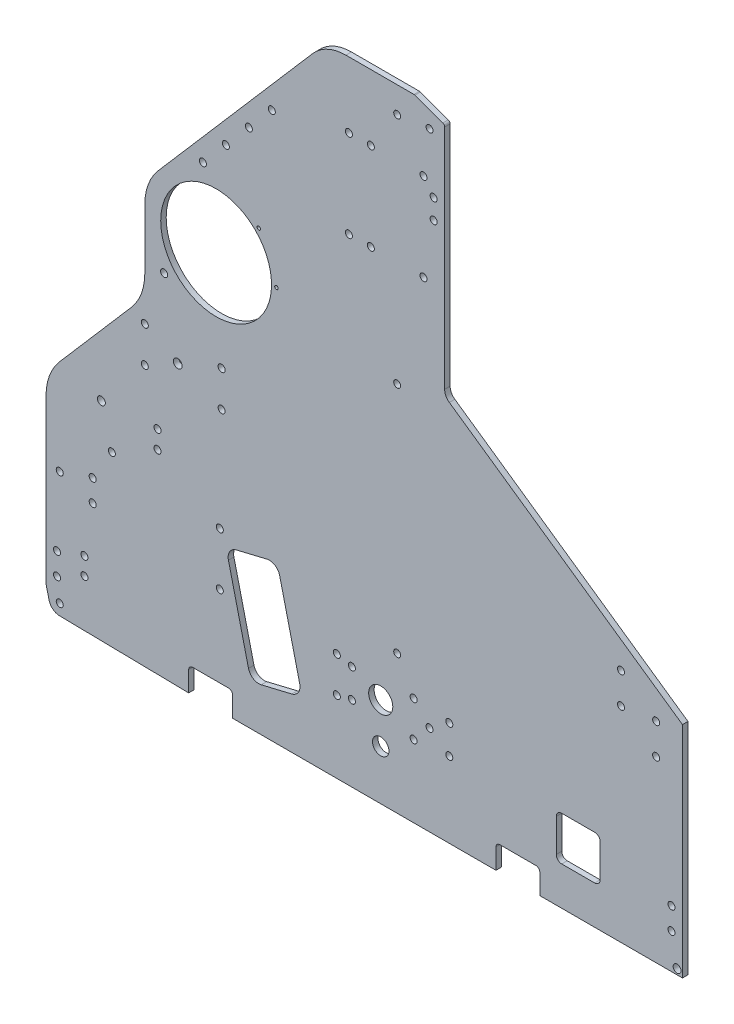
SolidWorks part; units mm, degrees
ref_plane "Front Plane" through (0, 0, 0) normal (0, 0, 1) x (1, 0, 0)
ref_plane "Top Plane" through (0, 0, 0) normal (0, 1, 0) x (1, 0, 0)
ref_plane "Right Plane" through (0, 0, 0) normal (1, 0, 0) x (0, 0, -1)
sketch "Sketch1" plane through (0, 0, 0) normal (0, 0, 1) x (1, 0, 0)
  line L0 (82.55, -20.32) -> (82.55, -6.35)
  line L2 (0, 0) -> (0, 157.48)
  line L4 (368.3, -20.32) -> (368.3, 106.68)
  line L5 (82.55, -6.35) -> (107.95, -6.35)
  line L6 (107.95, -6.35) -> (107.95, -20.32)
  line L7 (107.95, -20.32) -> (260.35, -20.32)
  line L8 (260.35, -20.32) -> (260.35, -6.35)
  line L9 (260.35, -6.35) -> (285.75, -6.35)
  line L10 (285.75, -6.35) -> (285.75, -20.32)
  line L11 (285.75, -20.32) -> (368.3, -20.32)
  line L12 (361.95, 12.7) -> (368.3, 12.7) construction
  line L13 (0, 0) -> (6.35, 0) construction
  line L14 (0.1896, -7.8901) -> (1.7771, -14.2401)
  line L15 (7.8295, -19.0491) -> (82.55, -20.32)
  line L16 (0, 0) -> (0, -6.35)
  line L17 (76.2, 141.605) -> (79.375, 141.605) construction
  line L18 (57.15, 131.2863) -> (101.6, 131.2862) construction
  line L19 (57.15, 131.2863) -> (57.15, 151.9238) construction
  line L20 (101.6, 131.2862) -> (101.6, 151.9237) construction
  line L21 (57.15, 151.9238) -> (101.6, 151.9237) construction
  line L22 (57.15, 131.2863) -> (101.6, 151.9237) construction
  line L23 (101.6, 131.2862) -> (57.15, 151.9238) construction
  line L25 (203.2, 59.805) -> (203.2, 194.805) construction
  line L26 (203.2, 194.805) -> (203.2, 329.805) construction
  line L27 (355.6, 332.105) -> (330.2, 332.105) construction
  line L28 (330.2, 332.105) -> (330.2, 217.805) construction
  line L29 (330.2, 217.805) -> (355.6, 217.805) construction
  line L30 (355.6, 217.805) -> (355.6, 332.105) construction
  line L31 (203.2, 344.805) -> (203.2, 194.805) construction
  line L32 (50.8, 332.105) -> (76.2, 332.105) construction
  line L33 (76.2, 332.105) -> (76.2, 217.805) construction
  line L34 (50.8, 217.805) -> (50.8, 332.105) construction
  line L35 (76.2, 217.805) -> (50.8, 217.805) construction
  line L36 (213.2, 344.805) -> (230.6638, 338.455)
  line L37 (203.2, 344.805) -> (161.925, 344.805)
  line L38 (203.2, 344.805) -> (213.2, 344.805)
  line L39 (348.5362, 344.805) -> (413.4623, 344.805)
  line L40 (348.5362, 344.805) -> (230.6638, 344.805) construction
  line L42 (161.925, 344.805) -> (0, 157.48)
  line L44 (230.6638, 338.455) -> (230.6638, 202.565)
  line L45 (230.6638, 202.565) -> (368.3, 106.68)
  line L46 (213.2, 344.805) -> (-141.0713, 344.805) construction
  circle A0 centre (6.35, 0) radius 2.032
  circle A1 centre (6.35, 12.7) radius 2.032
  circle A2 centre (361.95, 0) radius 2.032
  circle A3 centre (361.95, 12.7) radius 2.032
  arc A5 (1.7771, -14.2401) -> (7.8295, -19.0491) centre (7.9375, -12.7) ccw
  circle A6 centre (7.9375, -12.7) radius 2.032
  arc A7 (0, -6.35) -> (0.1896, -7.8901) centre (6.35, -6.35) ccw
  circle A8 centre (38.1, 78.105) radius 2.032
  circle A9 centre (76.2, 141.605) radius 2.54
  circle A10 centre (101.6, 131.2862) radius 2.032
  circle A11 centre (101.6, 151.9237) radius 2.032
  circle A12 centre (57.15, 151.9238) radius 2.032
  circle A13 centre (57.15, 131.2863) radius 2.032
  circle A15 centre (203.2, 59.805) radius 2
  circle A16 centre (203.2, 194.805) radius 2
  circle A17 centre (203.2, 329.805) radius 2
  circle A18 centre (63.5, 313.055) radius 2.032
  circle A20 centre (355.6, 332.105) radius 2.032
  circle A21 centre (330.2, 332.105) radius 2.032
  circle A22 centre (355.6, 217.805) radius 2.032
  circle A23 centre (330.2, 217.805) radius 2.032
  circle A24 centre (50.8, 332.105) radius 2.032
  circle A25 centre (76.2, 332.105) radius 2.032
  circle A26 centre (50.8, 217.805) radius 2.032
  circle A27 centre (76.2, 217.805) radius 2.032
  circle A28 centre (221.9319, 332.105) radius 2
  circle A29 centre (224.3138, 298.831) radius 2.032
  circle A30 centre (353.06, 100.7351) radius 2.032
  circle A31 centre (332.74, 115.9751) radius 2.032
  circle A32 centre (332.74, 98.1951) radius 2.032
  circle A33 centre (353.06, 82.9551) radius 2.032
  circle A34 centre (117.3562, 280.4276) radius 2.032
  circle A35 centre (104.0678, 265.0548) radius 2.032
  circle A36 centre (90.7795, 249.682) radius 2.032
  circle A38 centre (130.6445, 295.8004) radius 2.032
  circle A39 centre (68.326, 182.9237) radius 2.032
  circle A40 centre (224.3138, 287.401) radius 2.032
  point P82 (203.2, 344.805)
  point P83 (221.9319, 341.63)
  point P90 (368.3, 62.484)
  dimension "D6" = 4.064
  dimension "D10" = 6.35
  dimension "D11" = 4.064
  dimension "D17" = 38.1
  dimension "D27" = 4
  dimension "D31" = 4.064
  dimension "D32" = 41.275
  dimension "D36" = 4.064
  dimension "D47" = 39.624
  dimension "D48" = 4.064
  dimension "D25" = 5.08
  dimension "D26" = 4.064
  dimension "D52" = 4.064
  dimension "D65" = 4.064
  dimension "D2" = 127
  dimension "D3" = 13.97
  dimension "D4" = 25.4
  dimension "D5" = 152.4
  dimension "D7" = 12.7
  dimension "D8" = 6.35
  dimension "D9" = 20.32
  dimension "D12" = 12.7
  dimension "D13" = 1.5875
  dimension "D14" = 82.55
  dimension "D15" = 368.3
  dimension "D16" = 6.35
  dimension "D18" = 98.425
  dimension "D19" = 38.1
  dimension "D20" = 63.5
  dimension "D21" = 3.175
  dimension "D22" = 270
  dimension "D23" = 20.6375
  dimension "D24" = 44.45
  dimension "D28" = 135
  dimension "D29" = 12.7
  dimension "D30" = 15
  dimension "D33" = 63.5
  dimension "D34" = 27.4638
  dimension "D35" = 12.7
  dimension "D37" = 114.3
  dimension "D38" = 25.4
  dimension "D39" = 12.7
  dimension "D40" = 157.48
  dimension "D41" = 142.24
  dimension "D42" = 365.125
  dimension "D43" = 10
  dimension "D44" = 6.35
  dimension "D45" = 31.75
  dimension "D46" = 6.35
  dimension "D49" = 6.35
  dimension "D50" = 203.2
  dimension "D51" = 15.24
  dimension "D53" = 17.78
  dimension "D54" = 17.78
  dimension "D55" = 20.32
  dimension "D56" = 15.24
  dimension "D57" = 92.202
  dimension "D58" = 8.382
  dimension "D59" = 20.32
  dimension "D60" = 20.32
  dimension "D61" = 8.382
  dimension "D62" = 20.32
  dimension "D63" = 8.382
  dimension "D64" = 8.382
  dimension "D66" = 35.052
  dimension "D67" = 68.326
  dimension "D68" = 11.43
extrude "Boss-Extrude1" add sketch "Sketch1" along normal blind 3.175 contours L16 A7 L14 A5 L15 L2 A0 A1 A6 region at (171.3489, 119.5243, 0)
fillet "Fillet1" radius 2.286 4 edges at (285.75, -6.35, 1.5875) (107.95, -6.35, 1.5875) (260.35, -6.35, 1.5875) (82.55, -6.35, 1.5875)
fillet "Fillet2" radius 6.35 1 edges at (230.6638, 202.565, 1.5875)
sketch "Sketch2" plane through (0, 0, 0) normal (0, 0, -1) x (-1, 0, 0)
  circle A0 centre (-100.5528, 71.086) radius 2.032 construction
  circle A1 centre (-100.5528, 40.606) radius 2.032 construction
  circle A2 centre (-22.225, 18.2025) radius 2.032 construction
  circle A3 centre (-22.225, 8.0425) radius 2.032 construction
  circle A4 centre (-100.5528, 71.086) radius 2.032
  circle A5 centre (-100.5528, 40.606) radius 2.032
  circle A6 centre (-22.225, 18.2025) radius 2.032
  circle A7 centre (-22.225, 8.0425) radius 2.032
extrude "Cut-Extrude1" cut sketch "Sketch2" against normal through all
fillet "Fillet3" radius 1.5875 2 edges at (230.6638, 338.455, 1.5875) (213.2, 344.805, 1.5875)
sketch "Sketch3" plane through (0, 0, 3.175) normal (0, 0, 1) x (1, 0, 0)
  line L0 (132.9524, 63.2646) -> (132.7215, 64.2281) construction
  line L1 (128.3814, 66.8897) -> (110.6828, 62.6472) construction
  line L2 (114.5132, 58.4237) -> (126.8822, 61.3887) construction
  line L3 (108.0212, 58.3071) -> (108.2522, 57.3436) construction
  line L4 (131.2006, 57.703) -> (140.0164, 20.9265) construction
  line L5 (144.0993, 16.7636) -> (132.9524, 63.2646) construction
  line L6 (108.2522, 57.3436) -> (119.3991, 10.8426) construction
  line L7 (121.1509, 16.4042) -> (112.3351, 53.1807) construction
  line L8 (119.3991, 10.8426) -> (119.6301, 9.8791) construction
  line L9 (144.3303, 15.8001) -> (144.0993, 16.7636) construction
  line L10 (137.8383, 15.6835) -> (125.4694, 12.7185) construction
  line L11 (123.9701, 7.2175) -> (141.6687, 11.4601) construction
  line L12 (132.9524, 63.2646) -> (132.7215, 64.2281)
  line L13 (128.3814, 66.8897) -> (110.6828, 62.6472)
  line L14 (114.5132, 58.4237) -> (126.8822, 61.3887)
  line L15 (108.0212, 58.3071) -> (108.2522, 57.3436)
  line L16 (131.2006, 57.703) -> (140.0164, 20.9265)
  line L17 (144.0993, 16.7636) -> (132.9524, 63.2646)
  line L18 (108.2522, 57.3436) -> (119.3991, 10.8426)
  line L19 (121.1509, 16.4042) -> (112.3351, 53.1807)
  line L20 (119.3991, 10.8426) -> (119.6301, 9.8791)
  line L21 (144.3303, 15.8001) -> (144.0993, 16.7636)
  line L22 (137.8383, 15.6835) -> (125.4694, 12.7185)
  line L23 (123.9701, 7.2175) -> (141.6687, 11.4601)
  line L24 (127.7894, 69.3598) -> (110.0908, 65.1172)
  line L25 (105.5512, 57.715) -> (105.7822, 56.7515)
  line L26 (105.7822, 56.7515) -> (116.9291, 10.2505)
  line L27 (116.9291, 10.2505) -> (117.16, 9.287)
  line L28 (124.5622, 4.7475) -> (142.2608, 8.99)
  line L29 (146.8003, 16.3922) -> (146.5694, 17.3557)
  line L30 (146.5694, 17.3557) -> (135.4225, 63.8567)
  line L31 (135.4225, 63.8567) -> (135.1915, 64.8202)
  line L32 (14.605, -0.1369) -> (103.7278, 32.3011) construction
  line L33 (14.605, -0.1369) -> (103.7278, 32.3011)
  line L34 (0, -6.35) -> (0, 157.48) construction
  line L35 (-39.6666, 74.7152) -> (103.7278, 126.9065) construction
  line L36 (26.9875, 46.9531) -> (26.9875, 59.6531) construction
  line L37 (107.95, -20.32) -> (260.35, -20.32) construction
  line L38 (64.5259, 92.5258) -> (64.5259, 102.9405) construction
  arc A0 (132.7215, 64.2281) -> (128.6308, 66.9403) centre (129.2206, 63.3889) ccw construction
  arc A1 (110.6828, 62.6472) -> (110.4377, 62.5791) centre (111.522, 59.1463) ccw construction
  arc A2 (128.6308, 66.9403) -> (128.3814, 66.8897) centre (129.2206, 63.3889) ccw construction
  arc A3 (110.4377, 62.5791) -> (108.0212, 58.3071) centre (111.522, 59.1463) ccw construction
  arc A4 (119.6301, 9.8791) -> (123.7207, 7.1669) centre (123.1309, 10.7183) ccw construction
  arc A5 (141.9139, 11.5281) -> (144.3303, 15.8001) centre (140.8295, 14.9609) ccw construction
  arc A6 (141.6687, 11.4601) -> (141.9139, 11.5281) centre (140.8295, 14.9609) ccw construction
  arc A7 (123.7207, 7.1669) -> (123.9701, 7.2175) centre (123.1309, 10.7183) ccw construction
  arc A8 (132.7215, 64.2281) -> (128.6308, 66.9403) centre (129.2206, 63.3889) ccw
  arc A9 (110.6828, 62.6472) -> (110.4377, 62.5791) centre (111.522, 59.1463) ccw
  arc A10 (128.6308, 66.9403) -> (128.3814, 66.8897) centre (129.2206, 63.3889) ccw
  arc A11 (110.4377, 62.5791) -> (108.0212, 58.3071) centre (111.522, 59.1463) ccw
  arc A12 (119.6301, 9.8791) -> (123.7207, 7.1669) centre (123.1309, 10.7183) ccw
  arc A13 (141.9139, 11.5281) -> (144.3303, 15.8001) centre (140.8295, 14.9609) ccw
  arc A14 (141.6687, 11.4601) -> (141.9139, 11.5281) centre (140.8295, 14.9609) ccw
  arc A15 (123.7207, 7.1669) -> (123.9701, 7.2175) centre (123.1309, 10.7183) ccw
  arc A16 (110.0908, 65.1172) -> (109.6726, 65.0012) centre (111.522, 59.1463) ccw
  arc A17 (109.6726, 65.0012) -> (105.5512, 57.715) centre (111.522, 59.1463) ccw
  arc A18 (117.16, 9.287) -> (124.1369, 4.6613) centre (123.1309, 10.7183) ccw
  arc A19 (124.1369, 4.6613) -> (124.5622, 4.7475) centre (123.1309, 10.7183) ccw
  arc A20 (142.2608, 8.99) -> (142.6789, 9.1061) centre (140.8295, 14.9609) ccw
  arc A21 (142.6789, 9.1061) -> (146.8003, 16.3922) centre (140.8295, 14.9609) ccw
  arc A22 (135.1915, 64.8202) -> (128.2147, 69.446) centre (129.2206, 63.3889) ccw
  arc A23 (128.2147, 69.446) -> (127.7894, 69.3598) centre (129.2206, 63.3889) ccw
  circle A26 centre (133.35, 208.2281) radius 1.016 construction
  circle A33 centre (26.9875, 46.9531) radius 2.032
  circle A34 centre (26.9875, 59.6531) radius 2.032
  circle A35 centre (7.9375, 53.3031) radius 2.032
  circle A37 centre (32.0306, 100.8109) radius 31.75 construction
  circle A38 centre (32.0306, 100.8109) radius 2.286
  circle A39 centre (123.1207, 232.9238) radius 1.016 construction
  circle A40 centre (64.5259, 102.9405) radius 2.032
  circle A41 centre (64.5259, 92.5258) radius 2.032
  circle A42 centre (133.35, 208.2281) radius 1.016
  circle A43 centre (123.1207, 232.9238) radius 1.016
  ellipse E0 centre (124.5974, 48.8487) end of major axis (128.5376, 61.3578) minor radius 6 (131.2006, 57.703) -> (126.8822, 61.3887) ccw construction
  ellipse E1 centre (122.2349, 48.2824) end of major axis (113.0518, 57.6456) minor radius 6 (114.5132, 58.4237) -> (112.3351, 53.1807) ccw construction
  ellipse E2 centre (127.7541, 25.2585) end of major axis (131.6942, 37.7675) minor radius 6 (121.1509, 16.4042) -> (125.4694, 12.7185) ccw construction
  ellipse E3 centre (130.1166, 25.8248) end of major axis (139.2998, 16.4616) minor radius 6 (137.8383, 15.6835) -> (140.0164, 20.9265) ccw construction
  ellipse E4 centre (124.5974, 48.8487) end of major axis (120.6573, 36.3397) minor radius 6 (131.2006, 57.703) -> (126.8822, 61.3887) ccw
  ellipse E5 centre (122.2349, 48.2824) end of major axis (131.4181, 38.9192) minor radius 6 (114.5132, 58.4237) -> (112.3351, 53.1807) ccw
  ellipse E6 centre (127.7541, 25.2585) end of major axis (131.6942, 37.7675) minor radius 6 (121.1509, 16.4042) -> (125.4694, 12.7185) ccw
  ellipse E7 centre (130.1166, 25.8248) end of major axis (139.2998, 16.4616) minor radius 6 (137.8383, 15.6835) -> (140.0164, 20.9265) ccw
  point P93 (26.9875, 53.3031)
  point P115 (32.0306, 100.8109)
  dimension "D3" = 63.5
  dimension "D4" = 4.572
  dimension "D8" = 4.064
  dimension "D2" = 88.9
  dimension "D5" = 7.9375
  dimension "D6" = 19.05
  dimension "D7" = 73.6231
  dimension "D9" = 12.7
  dimension "D10" = 10.4147
  dimension "D11" = 37.5384
  dimension "D12" = 45.5727
  dimension "D1" = 2.54
extrude "Cut-Extrude2" cut sketch "Sketch3" against normal through all contours A22 A23 L24 A16 A17 L25 L26 L27 A18 A19 L28 A20 A21 L29 L30 L31 A15 A12 L20 L18 L15 A11 A9 L13 A10 A8 L12 L17 L21 A13 A14 L23 | A12 A15 L23 A14 A13 L21 L17 L12 A8 A10 L13 A9 A11 L15 L18 L20 E7 L22 E6 L19 E5 L14 E4 L16 | L22 E7 L16 E4 L14 E5 L19 E6 | A38 | A41 | A40 | A35 | A34 | A33 | A43 | A42 region at (137.844, 39.8506, 3.175) region at (126.1758, 37.0536, 3.175) region at (128.1544, 68.6507, 3.175) region at (32.0306, 100.8109, 3.175) region at (64.5259, 102.9405, 3.175) region at (64.5259, 92.5258, 3.175)
sketch "Sketch4" plane through (0, 0, 3.175) normal (0, 0, 1) x (1, 0, 0)
  line L0 (57.15, 151.9238) -> (101.6, 151.9237) construction
  line L1 (168.275, 21.4312) -> (212.725, 21.4312) construction
  line L2 (168.275, 21.4312) -> (168.275, 42.0687) construction
  line L3 (168.275, 42.0687) -> (212.725, 42.0687) construction
  line L4 (212.725, 21.4312) -> (212.725, 42.0687) construction
  line L5 (168.275, 21.4312) -> (212.725, 42.0687) construction
  line L6 (168.275, 42.0687) -> (212.725, 21.4312) construction
  line L7 (57.15, 131.2863) -> (57.15, 151.9238) construction
  line L8 (107.95, -20.32) -> (260.35, -20.32) construction
  line L9 (193.675, 31.75) -> (177.005, 31.75) construction
  line L10 (190.5, 31.75) -> (193.675, 31.75) construction
  line L11 (6.35, 12.7) -> (361.95, 12.7) construction
  line L12 (107.95, -6.35) -> (107.95, -20.32) construction
  line L13 (193.675, 31.75) -> (220.6625, 31.75) construction
  line L14 (177.005, 23.4569) -> (177.005, 40.0431) construction
  line L15 (213.2, 44.805) -> (193.2, 44.805) construction
  line L16 (213.2, 44.805) -> (213.2, 344.805) construction
  line L17 (213.2, 344.805) -> (193.2, 344.805) construction
  line L18 (193.2, 44.805) -> (193.2, 344.805) construction
  line L19 (213.2, 44.805) -> (193.2, 344.805) construction
  line L20 (213.2, 344.805) -> (193.2, 44.805) construction
  line L21 (226.9319, 332.105) -> (226.9319, 31.75) construction
  line L22 (237.33, 40.0431) -> (233.3612, 40.0431) construction
  line L23 (237.33, 23.4569) -> (233.3612, 23.4569) construction
  circle A0 centre (168.275, 42.0687) radius 2.032
  circle A1 centre (212.725, 42.0687) radius 2.032
  circle A2 centre (212.725, 21.4312) radius 2.032
  circle A3 centre (168.275, 21.4312) radius 2.032
  circle A4 centre (193.675, 31.75) radius 6.985
  circle A7 centre (220.6625, 31.75) radius 14.2875 construction
  circle A8 centre (193.675, 31.75) radius 12.7 construction
  circle A9 centre (177.005, 40.0431) radius 2.032
  circle A10 centre (177.005, 23.4569) radius 2.032
  circle A11 centre (237.33, 40.0431) radius 2.032 construction
  circle A12 centre (237.33, 23.4569) radius 2.032 construction
  circle A13 centre (193.675, 8.4667) radius 4.7625
  circle A14 centre (221.9319, 31.75) radius 2.032
  circle A15 centre (221.9319, 31.75) radius 5 construction
  circle A16 centre (221.9319, 332.105) radius 5 construction
  circle A17 centre (233.3612, 23.4569) radius 2.032
  circle A18 centre (233.3612, 40.0431) radius 2.032
  point P0 (190.5, 31.75)
  point P26 (203.2, 194.805)
  point P38 (177.005, 31.75)
  dimension "D1" = 4.064
  dimension "D4" = 13.97
  dimension "D7" = 9.525
  dimension "D10" = 25.4
  dimension "D11" = 28.575
  dimension "D16" = 10
  dimension "D17" = 4.064
  dimension "D18" = 10
  dimension "D2" = 52.07
  dimension "D3" = 3.175
  dimension "D5" = 82.55
  dimension "D6" = 26.9875
  dimension "D8" = 20
  dimension "D9" = 300
  dimension "D12" = 16.67
  dimension "D13" = 16.5862
  dimension "D14" = 60.325
  dimension "D15" = 23.2833
  dimension "D19" = 3.9688
extrude "Cut-Extrude3" cut sketch "Sketch4" against normal through all
sketch "Sketch5" plane through (0, 0, 0) normal (0, 0, -1) x (-1, 0, 0)
  line L0 (-57.15, 223.5947) -> (-57.15, 165.3337)
  line L1 (-161.925, 344.805) -> (-52.7201, 218.4699) construction
  line L2 (-57.15, 165.3337) -> (0, 99.219)
  line L3 (0, -6.35) -> (0, 157.48) construction
  line L5 (-50.4199, 215.8089) -> (0, 157.48) construction
  line L6 (-57.15, 223.5947) -> (0, 157.48)
  line L7 (0, 157.48) -> (0, 99.219)
  line L8 (-365.1708, -17.1908) -> (-368.3, -17.1908) construction
  line L9 (-365.1708, -17.1908) -> (-365.1708, -20.32) construction
  line L10 (-285.75, -20.32) -> (-368.3, -20.32) construction
  line L11 (-368.3, -20.32) -> (-368.3, 106.68) construction
  circle A0 centre (-98.425, 208.2281) radius 32.0675
  circle A2 centre (-365.1708, -17.1908) radius 2.286
  point P15 (-368.3, -17.1908)
  dimension "D3" = 64.135
  dimension "D7" = 4.572
  dimension "D1" = 38.1
  dimension "D2" = 57.15
  dimension "D4" = 41.275
  dimension "D5" = 41.275
  dimension "D6" = 3.1292
extrude "Cut-Extrude5" cut sketch "Sketch5" against normal through all contours A0 | L7 L6 L0 L2 | A2 region at (28.575, 161.4068, 0) region at (98.425, 208.2281, 0)
fillet "Fillet4" radius 31.75 3 edges at (0, 99.219, 1.5875) (57.15, 165.3337, 1.5875) (57.15, 223.5947, 1.5875)
sketch "Sketch6" plane through (0, 0, 3.175) normal (0, 0, 1) x (1, 0, 0)
  line L0 (285.75, -20.32) -> (368.3, -20.32) construction
  line L1 (298.45, 27.305) -> (317.5, 27.305)
  line L2 (295.275, 24.13) -> (295.275, 5.08)
  line L3 (298.45, 1.905) -> (317.5, 1.905)
  line L4 (320.675, 24.13) -> (320.675, 5.08)
  line L5 (295.275, 27.305) -> (320.675, 1.905) construction
  line L6 (295.275, 1.905) -> (320.675, 27.305) construction
  line L7 (368.3, -20.32) -> (368.3, 106.68) construction
  arc A0 (295.275, 5.08) -> (298.45, 1.905) centre (298.45, 5.08) ccw
  arc A1 (317.5, 1.905) -> (320.675, 5.08) centre (317.5, 5.08) ccw
  arc A2 (317.5, 27.305) -> (320.675, 24.13) centre (317.5, 24.13) cw
  arc A3 (298.45, 27.305) -> (295.275, 24.13) centre (298.45, 24.13) ccw
  point P0 (307.975, 14.605)
  dimension "D2" = 3.175
  dimension "D1" = 25.4
  dimension "D3" = 22.225
  dimension "D4" = 47.625
extrude "Cut-Extrude6" cut sketch "Sketch6" against normal through all
fillet "Fillet5" radius 25.4 1 edges at (161.925, 344.805, 1.5875)
sketch "Sketch8" plane through (0, 0, 0) normal (0, 0, -1) x (-1, 0, 0)
  circle A0 centre (-187.96, 306.705) radius 2.032 construction
  arc A1 (-176.3652, 304.9998) -> (-176.3652, 308.4102) centre (-175.26, 306.705) ccw construction
  arc A2 (-219.0586, 304.7695) -> (-219.0586, 308.6405) centre (-218.44, 306.705) ccw construction
  circle A3 centre (-205.74, 306.705) radius 2.032 construction
  arc A4 (-219.0586, 253.9695) -> (-219.0586, 257.8405) centre (-218.44, 255.905) ccw construction
  circle A5 centre (-205.74, 255.905) radius 2.032 construction
  circle A6 centre (-187.96, 255.905) radius 2.032 construction
  arc A7 (-176.3652, 254.1998) -> (-176.3652, 257.6102) centre (-175.26, 255.905) ccw construction
  circle A8 centre (-187.96, 306.705) radius 2.032
  arc A9 (-176.3652, 304.9998) -> (-176.3652, 308.4102) centre (-175.26, 306.705) ccw
  arc A10 (-219.0586, 304.7695) -> (-219.0586, 308.6405) centre (-218.44, 306.705) ccw
  circle A11 centre (-205.74, 306.705) radius 2.032
  arc A12 (-219.0586, 253.9695) -> (-219.0586, 257.8405) centre (-218.44, 255.905) ccw
  circle A13 centre (-205.74, 255.905) radius 2.032
  circle A14 centre (-187.96, 255.905) radius 2.032
  arc A15 (-176.3652, 254.1998) -> (-176.3652, 257.6102) centre (-175.26, 255.905) ccw
  circle A16 centre (-218.44, 306.705) radius 2.032
  circle A17 centre (-175.26, 306.705) radius 2.032
  circle A18 centre (-175.26, 255.905) radius 2.032
  circle A19 centre (-218.44, 255.905) radius 2.032
  circle A20 centre (-218.44, 306.705) radius 3.9688
  circle A21 centre (-205.74, 306.705) radius 3.9687
  circle A22 centre (-175.26, 306.705) radius 3.9687
  circle A23 centre (-218.44, 255.905) radius 3.9687
  circle A24 centre (-205.74, 255.905) radius 3.9687
  circle A25 centre (-187.96, 255.905) radius 3.9688
  circle A26 centre (-175.26, 255.905) radius 3.9687
  circle A27 centre (-187.96, 306.705) radius 3.9687
  dimension "D1" = 7.9375
extrude "Cut-Extrude7" cut sketch "Sketch8" against normal through all contours A10 A16 | A9 A17 | A15 A18 | A12 A19 | A8 | A14 region at (175.26, 306.705, 0) region at (218.44, 306.705, 0) region at (218.44, 255.905, 0) region at (175.26, 255.905, 0)
